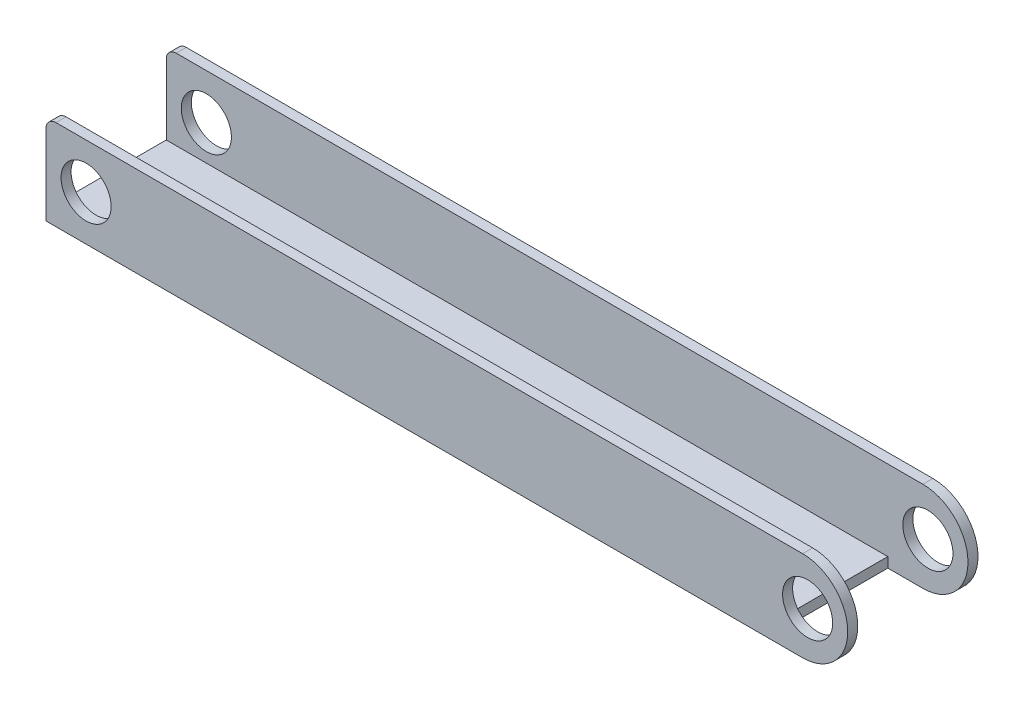
SolidWorks part; units mm, degrees
ref_plane "Front Plane" through (0, 0, 0) normal (0, 0, 1) x (1, 0, 0)
ref_plane "Top Plane" through (0, 0, 0) normal (0, 1, 0) x (1, 0, 0)
ref_plane "Right Plane" through (0, 0, 0) normal (1, 0, 0) x (0, 0, -1)
sketch "Sketch1" plane through (0, 0, 0) normal (1, 0, 0) x (0, 0, -1)
  line L0 (-27.5, 40) -> (-27.5, 0)
  line L1 (-27.5, 0) -> (27.5, 0)
  line L2 (27.5, 0) -> (27.5, 40)
  dimension "D1" = 55
  dimension "D2" = 40
extrude "Extrude-Thin1" add sketch "Sketch1" along normal mid plane 400 thin thin type one direction wall 5
sketch "Sketch3" plane through (0, 0, 0) normal (0, 0, 1) x (1, 0, 0)
  line L0 (0, 0) -> (0, 115.3057) construction
  line L1 (-200, 40) -> (-200, -5) construction
  line L2 (-200, 17.5) -> (-180, 17.5) construction
  circle A0 centre (-180, 17.5) radius 12.5
  circle A1 centre (180, 17.5) radius 12.5
  dimension "D2" = 25
  dimension "D1" = 20
extrude "Cut-Extrude1" cut sketch "Sketch3" against normal through all both and the other way through all
fillet "Fillet1" radius 5 2 edges at (-200, 40, -30) (-200, 40, 30)
sketch "Sketch4" plane through (0, -5, 0) normal (0, 1, 0) x (1, 0, 0)
  line L0 (200, 27.5) -> (200, -27.5)
  line L1 (200, -27.5) -> (160, -27.5)
  line L2 (200, -27.5) -> (-200, -27.5) construction
  line L3 (160, -27.5) -> (160, 27.5)
  line L4 (200, 27.5) -> (-200, 27.5) construction
  line L5 (160, 27.5) -> (200, 27.5)
  dimension "D1" = 40
extrude "Cut-Extrude2" cut sketch "Sketch4" along normal through all
fillet "Fillet2" 2 edges at (200, 40, -30) (200, -5, -30) type full round first side face at (2.5, 40, -30) second side face at (90, -5, 0) middle face at (200, 17.5, -30)
fillet "Fillet3" 2 edges at (200, 40, 30) (200, -5, 30) type full round first side face at (2.5, 40, 30) second side face at (84.375, -5, 0) middle face at (200, 17.5, 30)
